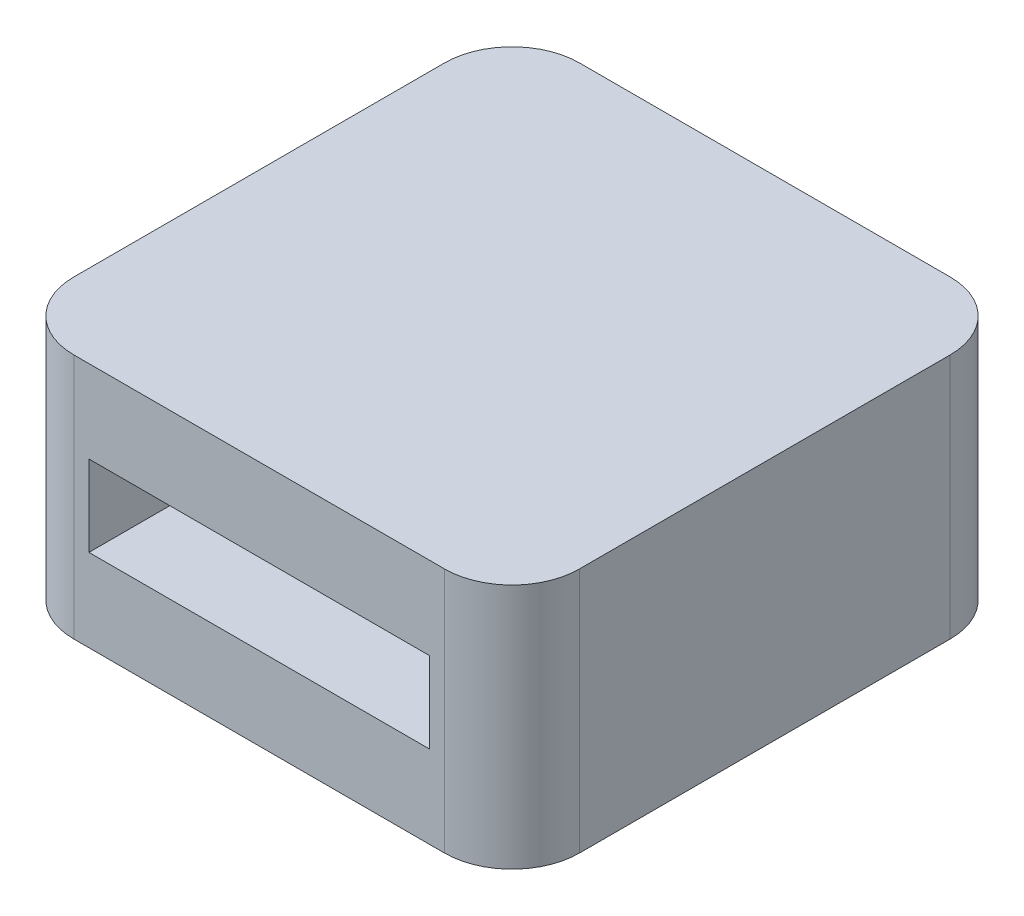
SolidWorks part; units mm, degrees
ref_plane "Front Plane" through (0, 0, 0) normal (0, 0, 1) x (1, 0, 0)
ref_plane "Top Plane" through (0, 0, 0) normal (0, 1, 0) x (1, 0, 0)
ref_plane "Right Plane" through (0, 0, 0) normal (1, 0, 0) x (0, 0, -1)
sketch "Profile Sketch" plane through (0, 0, 0) normal (0, 0, 1) x (1, 0, 0)
  line L0 (0, 1.2) -> (0, 3.65) construction
  line L1 (-5.05, -1.2) -> (5.05, -1.2)
  line L2 (-5.05, -1.2) -> (-5.05, 1.2)
  line L3 (-5.05, 1.2) -> (5.05, 1.2)
  line L4 (5.05, -1.2) -> (5.05, 1.2)
  line L5 (-5.05, -1.2) -> (5.05, 1.2) construction
  line L6 (-5.05, 1.2) -> (5.05, -1.2) construction
  line L7 (-7.5, -3.65) -> (7.5, -3.65)
  line L8 (-7.5, -3.65) -> (-7.5, 3.65)
  line L9 (-7.5, 3.65) -> (7.5, 3.65)
  line L10 (7.5, -3.65) -> (7.5, 3.65)
  line L11 (-7.5, -3.65) -> (7.5, 3.65) construction
  line L12 (-7.5, 3.65) -> (7.5, -3.65) construction
  line L13 (-5.05, 0) -> (-7.5, 0) construction
  point P0 (0, 0)
  point P6 (0, 0)
  dimension "D1" = 10.1
  dimension "D2" = 2.45
  dimension "D3" = 2.4
extrude "Profile Extrude" add sketch "Profile Sketch" along normal blind 15
fillet "Corner Fillets" radius 2 4 edges at (-7.5, 0, 0) (7.5, 0, 0) (7.5, 0, 15) (-7.5, 0, 15)
